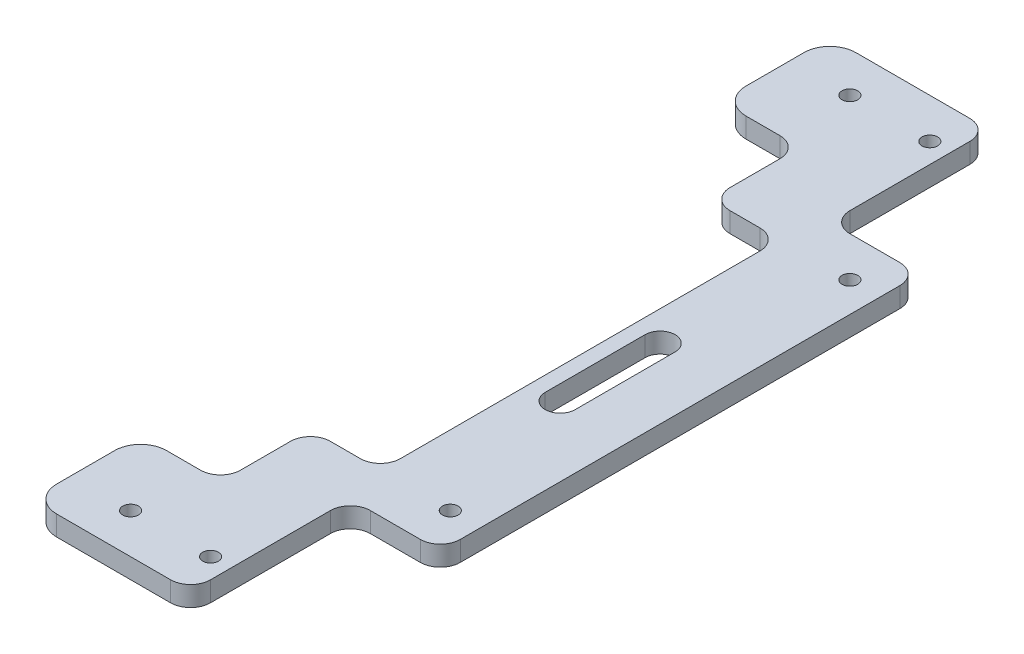
SolidWorks part; units mm, degrees
material "PC High Viscosity"
ref_plane "Front Plane" through (0, 0, 0) normal (0, 0, 1) x (1, 0, 0)
ref_plane "Top Plane" through (0, 0, 0) normal (0, 1, 0) x (1, 0, 0)
ref_plane "Right Plane" through (0, 0, 0) normal (1, 0, 0) x (0, 0, -1)
sketch "Sketch1" plane through (0, 0, 0) normal (0, 1, 0) x (1, 0, 0)
  line L0 (0, 0) -> (0, 50.8)
  line L5 (0, 50.8) -> (-28.575, 50.8)
  line L6 (-28.575, 50.8) -> (-28.575, 203.2)
  line L7 (-28.575, 203.2) -> (0, 203.2)
  line L8 (0, 203.2) -> (0, 254)
  line L9 (0, 254) -> (215.9, 254)
  line L10 (215.9, 254) -> (215.9, 203.2)
  line L11 (215.9, 203.2) -> (244.475, 203.2)
  line L12 (244.475, 203.2) -> (244.475, 50.8)
  line L13 (244.475, 50.8) -> (215.9, 50.8)
  line L14 (215.9, 50.8) -> (215.9, 0)
  line L15 (215.9, 0) -> (0, 0)
  line L16 (101.6, 219.075) -> (101.6, 34.925) construction
  line L17 (12.7, 219.075) -> (190.5, 219.075)
  line L18 (12.7, 219.075) -> (12.7, 34.925)
  line L19 (12.7, 34.925) -> (190.5, 34.925)
  line L20 (190.5, 219.075) -> (190.5, 34.925)
  line L21 (-9.525, 63.5) -> (12.7, 63.5)
  line L22 (-9.525, 63.5) -> (-9.525, 190.5)
  line L23 (-9.525, 190.5) -> (12.7, 190.5)
  line L24 (12.7, 63.5) -> (12.7, 190.5)
  line L25 (212.725, 190.5) -> (190.5, 190.5)
  line L26 (190.5, 63.5) -> (190.5, 190.5)
  line L27 (212.725, 63.5) -> (190.5, 63.5)
  line L28 (212.725, 63.5) -> (212.725, 190.5)
  line L29 (12.7, 127) -> (-9.525, 127) construction
  line L30 (-19.05, 111.125) -> (-19.05, 142.875) construction
  line L31 (-23.8125, 111.125) -> (-23.8125, 142.875)
  line L32 (-14.2875, 111.125) -> (-14.2875, 142.875)
  line L33 (222.25, 111.125) -> (222.25, 142.875) construction
  line L34 (227.0125, 111.125) -> (227.0125, 142.875)
  line L35 (217.4875, 111.125) -> (217.4875, 142.875)
  line L36 (12.7, 219.075) -> (12.7, 254) construction
  line L37 (12.7, 34.925) -> (12.7, 0) construction
  circle A0 centre (209.55, 241.3) radius 2.4892
  circle A1 centre (209.55, 12.7) radius 2.4892
  arc A2 (-23.8125, 111.125) -> (-14.2875, 111.125) centre (-19.05, 111.125) ccw
  arc A3 (-14.2875, 142.875) -> (-23.8125, 142.875) centre (-19.05, 142.875) ccw
  arc A4 (227.0125, 111.125) -> (217.4875, 111.125) centre (222.25, 111.125) cw
  arc A5 (217.4875, 142.875) -> (227.0125, 142.875) centre (222.25, 142.875) cw
  point P34 (-19.05, 127)
  point P44 (222.25, 127)
  dimension "D10" = 4.9784
  dimension "D1" = 177.8
  dimension "D5" = 12.7
  dimension "D6" = 25.4
  dimension "D7" = 152.4
  dimension "D8" = 22.225
  dimension "D9" = 19.05
  dimension "D11" = 12.7
  dimension "D12" = 12.7
  dimension "D13" = 6.35
  dimension "D14" = 12.7
  dimension "D15" = 9.525
  dimension "D16" = 9.525
  dimension "D17" = 31.75
  dimension "D2" = 254
  dimension "D3" = 184.15
extrude "Boss-Extrude1" add sketch "Sketch1" along normal mid plane 6.35 contours L15 L14 L13 L12 L11 L10 L9 L8 L7 L6 L5 L0 A1 A0 L28 L27 L20 L19 L18 L21 L22 L23 L17 L25 region at (3.7292, 0, -25.4)
fillet "Fillet1" radius 6.35 24 edges at (0, 0, 0) (0, 0, -50.8) (-28.575, 0, -50.8) (-28.575, 0, -203.2) (0, 0, -203.2) (0, 0, -254) (215.9, 0, -254) (215.9, 0, -203.2) (244.475, 0, -203.2) (244.475, 0, -50.8) (215.9, 0, -50.8) (215.9, 0, 0) (212.725, 0, -190.5) (190.5, 0, -190.5) (190.5, 0, -219.075) (12.7, 0, -219.075) (-9.525, 0, -190.5) (-9.525, 0, -63.5) (12.7, 0, -63.5) (12.7, 0, -34.925) (190.5, 0, -34.925) (190.5, 0, -63.5) (212.725, 0, -63.5) (12.7, 0, -190.5)
pattern_linear "LPattern1" count 8 spacing 25.4 along (-1, 0, 0) of face at (209.55, 3.175, -238.8108) of face at (209.55, 3.175, -10.2108)
sketch "Sketch2" plane through (0, 3.175, 0) normal (0, 1, 0) x (1, 0, 0)
  line L0 (6.35, 254) -> (209.55, 254) construction
  line L1 (165.1, 254) -> (-28.575, 254)
  line L2 (165.1, 254) -> (165.1, 0)
  line L3 (165.1, 0) -> (-28.575, 0)
  line L4 (-28.575, 254) -> (-28.575, 0)
  line L5 (209.55, 0) -> (6.35, 0) construction
  line L6 (-28.575, 57.15) -> (-28.575, 196.85) construction
  line L7 (234.95, 190.5) -> (234.95, 63.5) construction
  line L8 (244.475, 196.85) -> (244.475, 57.15) construction
  line L9 (217.4875, 111.125) -> (217.4875, 142.875) construction
  line L10 (222.25, 203.2) -> (238.125, 203.2) construction
  circle A1 centre (184.15, 241.3) radius 2.4892 construction
  circle A2 centre (234.95, 190.5) radius 2.4892
  circle A3 centre (234.95, 63.5) radius 2.4892
  point P16 (234.95, 127)
  point P17 (217.4875, 127)
  dimension "D1" = 19.05
  dimension "D2" = 4.9784
  dimension "D3" = 12.7
  dimension "D4" = 9.525
extrude "Cut-Extrude1" cut sketch "Sketch2" against normal through all
fillet "Fillet2" radius 8.255 4 edges at (165.1, 0, -219.075) (165.1, 0, -254) (165.1, 0, 0) (165.1, 0, -34.925)
equation "\"D14@Sketch1\"=\"D5@Sketch1\""
